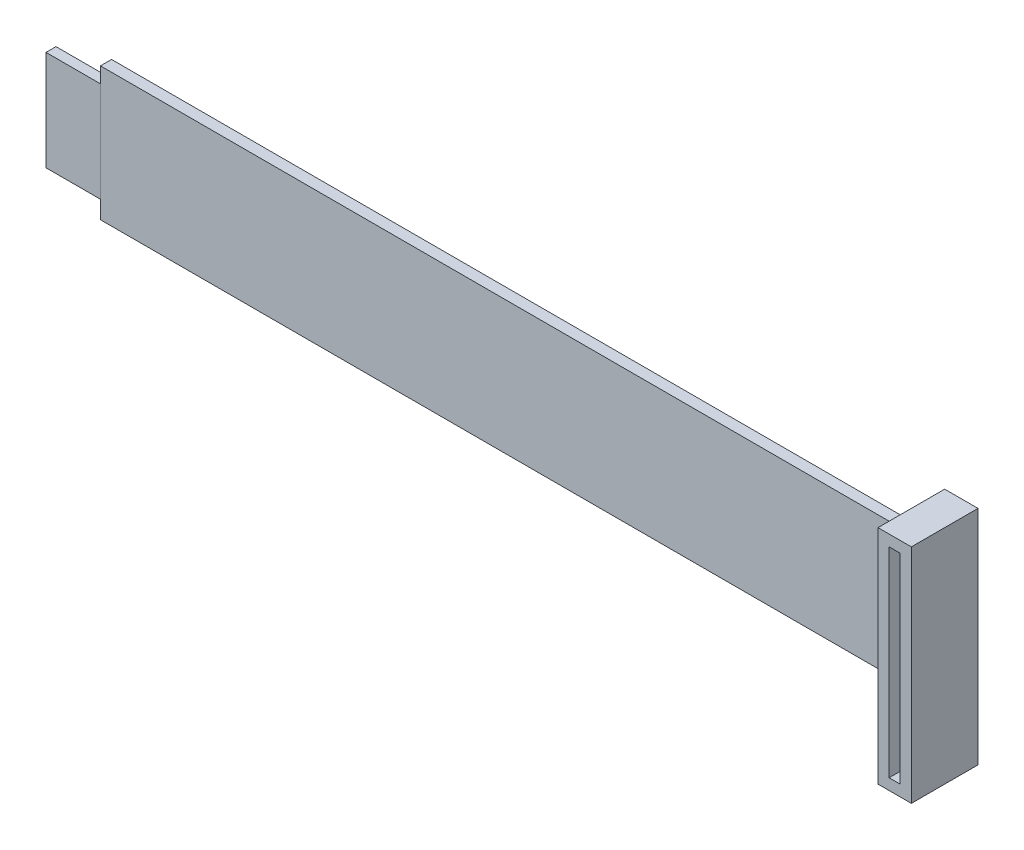
SolidWorks part; units mm, degrees
ref_plane "Alzado" through (0, 0, 0) normal (0, 0, 1) x (1, 0, 0)
ref_plane "Planta" through (0, 0, 0) normal (0, 1, 0) x (1, 0, 0)
ref_plane "Vista lateral" through (0, 0, 0) normal (1, 0, 0) x (0, 0, -1)
sketch "Croquis1" plane through (0, 0, 0) normal (0, 0, 1) x (1, 0, 0)
  line L0 (-8.5165, 1.2959) -> (1.4835, 1.2959)
  line L2 (-8.5165, 1.2959) -> (-8.5165, -18.7041)
  line L5 (1.4835, 1.2959) -> (1.4835, 3.2959)
  line L6 (1.4835, 3.2959) -> (151.4835, 3.2959)
  line L7 (151.4835, 3.2959) -> (151.4835, -20.7041)
  line L8 (151.4835, -20.7041) -> (1.4835, -20.7041)
  line L9 (1.4835, -20.7041) -> (1.4835, -18.7041)
  line L10 (1.4835, -18.7041) -> (-8.5165, -18.7041)
  dimension "D2" = 20
extrude "Saliente-Extruir1" add sketch "Croquis1" along normal blind 2
sketch "Croquis2" plane through (0, 0, 2) normal (0, 0, 1) x (1, 0, 0)
  line L0 (151.4835, 3.2959) -> (151.4835, 11.2959)
  line L1 (151.4835, 11.2959) -> (157.4835, 11.2959)
  line L2 (157.4835, 11.2959) -> (157.4835, -28.7041)
  line L3 (157.4835, -28.7041) -> (151.4835, -28.7041)
  line L4 (151.4835, -28.7041) -> (151.4835, 3.2959)
  line L6 (153.4835, 9.2959) -> (155.4835, 9.2959)
  line L7 (153.4835, 9.2959) -> (153.4835, -26.7041)
  line L8 (153.4835, -26.7041) -> (155.4835, -26.7041)
  line L9 (155.4835, 9.2959) -> (155.4835, -26.7041)
  dimension "D1" = 2
  dimension "D2" = 2
  dimension "D3" = 6
  dimension "D4" = 36
  dimension "D5" = 2
  dimension "D6" = 8
  dimension "D7" = 40
extrude "Saliente-Extruir2" add sketch "Croquis2" against normal up to vertex (2 mm away) up to point (151.4835, 3.2959, 0)
extrude "Saliente-Extruir3" add sketch "Croquis2<2>" along normal blind 10
sketch "Croquis2<2>" plane through (0, 0, 2) normal (0, 0, 1) x (1, 0, 0) same geometry as "Croquis2"
sketch "Croquis3" plane through (0, 0, 2) normal (0, 0, 1) x (1, 0, 0)
  line L0 (1.4835, 3.2959) -> (1.4835, 1.2959) construction
  line L1 (-8.5165, 1.2959) -> (1.4835, 1.2959)
  line L2 (-8.5165, 1.2959) -> (-8.5165, 0.2959)
  line L3 (-8.5165, 0.2959) -> (1.4835, 0.2959)
  line L4 (1.4835, 1.2959) -> (1.4835, 0.2959)
  line L6 (-8.5165, -18.7041) -> (1.4835, -18.7041)
  line L7 (-8.5165, -18.7041) -> (-8.5165, -17.7041)
  line L8 (-8.5165, -17.7041) -> (1.4835, -17.7041)
  line L9 (1.4835, -18.7041) -> (1.4835, -17.7041)
  dimension "D1" = 0
  dimension "D2" = 1
  dimension "D3" = 1
extrude "Cortar-Extruir1" cut sketch "Croquis3" against normal up to vertex (2 mm away) up to point (1.4835, -18.7041, 0)
sketch "Croquis4" plane through (0, -17.7041, 0) normal (0, -1, 0) x (1, 0, 0)
  line L1 (1.4835, 0) -> (1.4835, 2) construction
  line L2 (-8.5165, 2) -> (1.4835, 2)
  line L3 (-8.5165, 2) -> (-8.5165, 1.8)
  line L4 (-8.5165, 1.8) -> (1.4835, 1.8)
  line L5 (1.4835, 2) -> (1.4835, 1.8)
  dimension "D1" = 0.2
extrude "Cortar-Extruir2" cut sketch "Croquis4" against normal up to vertex (18 mm away) up to point (-8.5165, 0.2959, 2)
